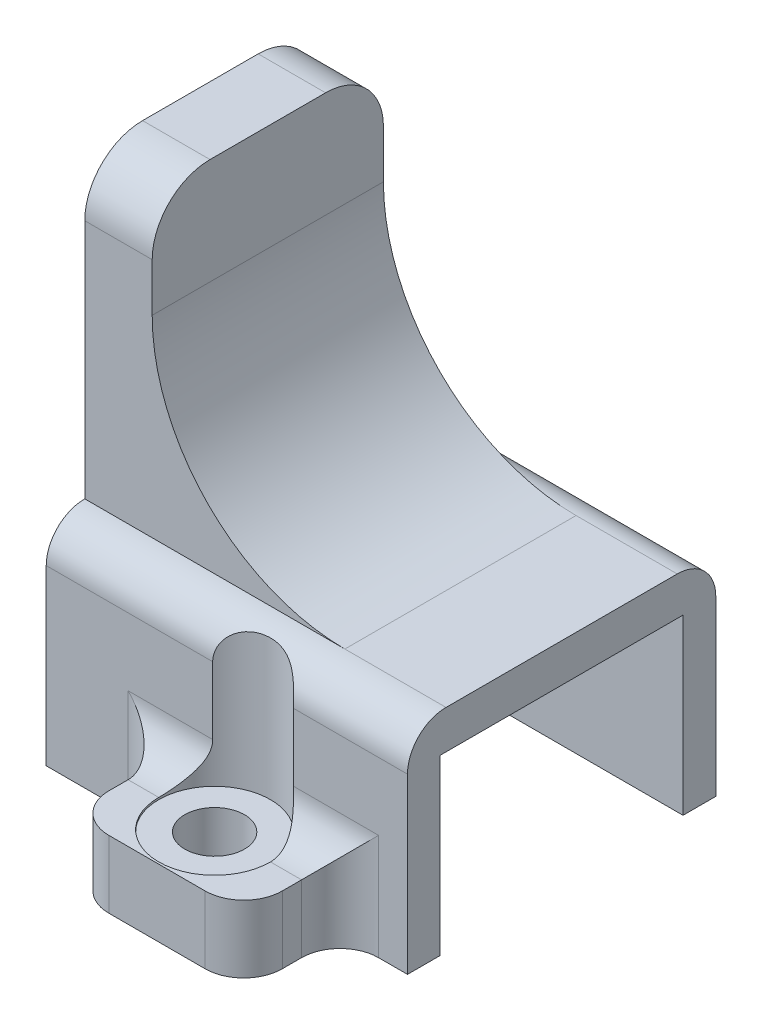
SolidWorks part; units mm, degrees
ref_plane "Alzado" through (0, 0, 0) normal (0, 0, 1) x (1, 0, 0)
ref_plane "Planta" through (0, 0, 0) normal (0, 1, 0) x (1, 0, 0)
ref_plane "Vista lateral" through (0, 0, 0) normal (1, 0, 0) x (0, 0, -1)
sketch "Croquis1" plane through (0, 0, 0) normal (0, 1, 0) x (1, 0, 0)
  line L1 (0, 0) -> (18.75, 0)
  line L2 (0, 0) -> (0, 16)
  line L3 (0, 16) -> (18.75, 16)
  line L4 (18.75, 0) -> (18.75, 16)
  dimension "D1" = 18.75
  dimension "D2" = 16
extrude "Saliente-Extruir1" add sketch "Croquis1" along normal blind 10
sketch "Croquis2" plane through (0, 0, 0) normal (0, -1, 0) x (1, 0, 0)
  line L19 (18.75, 0) -> (18.75, -16) construction
  line L20 (0, -16) -> (0, 0) construction
  line L22 (0, 0) -> (18.75, 0) construction
  line L23 (0, -1.7) -> (18.75, -1.7)
  line L24 (0, -1.7) -> (0, -14.3)
  line L25 (0, -14.3) -> (18.75, -14.3)
  line L26 (18.75, -1.7) -> (18.75, -14.3)
  line L27 (18.75, -16) -> (0, -16) construction
  point P10 (9.375, 0)
  dimension "D1" = 1.7
  dimension "D2" = 1.7
extrude "Cortar-Extruir1" cut sketch "Croquis2" against normal blind 8
sketch "Croquis3" plane through (0, 0, 0) normal (0, 0, 1) x (1, 0, 0)
  line L0 (0, 0) -> (18.75, 0) construction
  line L1 (6.25, 0) -> (15.25, 0)
  line L2 (6.25, 0) -> (6.25, 2.5)
  line L3 (6.25, 2.5) -> (15.25, 2.5)
  line L4 (15.25, 0) -> (15.25, 2.5)
  line L5 (18.75, 10) -> (18.75, 0) construction
  dimension "D1" = 2.5
  dimension "D2" = 3.5
  dimension "D3" = 9
extrude "Saliente-Extruir2" add sketch "Croquis3" along normal blind 5
sketch "Croquis4" plane through (0, 2.5, 0) normal (0, 1, 0) x (1, 0, 0)
  line L0 (18.75, 0) -> (18.75, 16) construction
  line L1 (15.25, 0) -> (6.25, 0) construction
  circle A0 centre (10.74, -2) radius 1.55
  dimension "D1" = 3.1
  dimension "D2" = 8.01
  dimension "D3" = 2
extrude "Cortar-Extruir2" cut sketch "Croquis4" against normal up to surface (2.5 mm away) up to face at (9.375, 0, -15.15)
fillet "Redondeo1" radius 2 7 edges at (9.375, 10, -16) (9.375, 10, 0) (6.25, 1.25, 5) (15.25, 1.25, 5) (10.75, 2.5, 0) (15.25, 1.25, 0) (6.25, 1.25, 0)
sketch "Croquis5" plane through (0, 10, 0) normal (0, 1, 0) x (1, 0, 0)
  circle A0 centre (10.74, -2) radius 2.9
  dimension "D1" = 5.8
extrude "Cortar-Extruir3" cut sketch "Croquis5" against normal blind 7.6
sketch "Croquis6" plane through (0, 10, 0) normal (0, 1, 0) x (1, 0, 0)
  line L0 (0, 2) -> (18.75, 2) construction
  line L1 (0, 14) -> (3.5, 14)
  line L2 (0, 14) -> (0, 2)
  line L3 (0, 2) -> (3.5, 2)
  line L4 (3.5, 14) -> (3.5, 2)
  dimension "D1" = 3.5
extrude "Saliente-Extruir3" add sketch "Croquis6" along normal blind 15.5
fillet "Redondeo2" radius 10 1 edges at (3.5, 10, -8)
fillet "Redondeo3" radius 3 2 edges at (1.75, 25.5, -14) (1.75, 25.5, -2)
sketch "Croquis7" plane through (0, 0, 0) normal (-1, 0, 0) x (0, 0, 1)
  line L0 (-14.3, 0) -> (-14.3, 8)
  line L1 (-14.3, 8) -> (-1.7, 8)
  line L2 (-1.7, 8) -> (-1.7, 0)
  line L10 (-5, 25.5) -> (-11, 25.5)
  line L11 (-14, 22.5) -> (-14, 10)
  line L12 (-16, 8) -> (-16, 0)
  line L13 (-16, 0) -> (-14.3, 0)
  line L14 (-14.3, 0) -> (-14.3, 8)
  line L15 (-14.3, 8) -> (-1.7, 8)
  line L16 (-1.7, 8) -> (-1.7, 0)
  line L17 (-1.7, 0) -> (0, 0)
  line L18 (0, 0) -> (0, 8)
  line L19 (-2, 10) -> (-2, 22.5)
  line L20 (-5, 25.5) -> (-11, 25.5)
  line L21 (-14, 22.5) -> (-14, 10)
  line L22 (-16, 8) -> (-16, 0)
  line L23 (-16, 0) -> (-14.3, 0)
  line L27 (-1.7, 0) -> (0, 0)
  line L28 (0, 0) -> (0, 8)
  line L29 (-2, 10) -> (-2, 22.5)
  arc A4 (-11, 25.5) -> (-14, 22.5) centre (-11, 22.5) ccw
  arc A5 (-14, 10) -> (-16, 8) centre (-14, 8) ccw
  arc A6 (0, 8) -> (-2, 10) centre (-2, 8) ccw
  arc A7 (-2, 22.5) -> (-5, 25.5) centre (-5, 22.5) ccw
  arc A8 (-11, 25.5) -> (-14, 22.5) centre (-11, 22.5) ccw
  arc A9 (-14, 10) -> (-16, 8) centre (-14, 8) ccw
  arc A10 (0, 8) -> (-2, 10) centre (-2, 8) ccw
  arc A11 (-2, 22.5) -> (-5, 25.5) centre (-5, 22.5) ccw
  dimension "D1" = 0
sketch "Croquis8" plane through (0, 0, 0) normal (0, -1, 0) x (1, 0, 0)
  line L4 (18.75, -14.3) -> (-5, -14.3)
  line L5 (-5, -14.3) -> (-5, -16)
  line L6 (-5, -16) -> (18.75, -16)
  line L7 (18.75, -16) -> (18.75, -14.3)
  line L8 (13.25, 5) -> (8.25, 5)
  line L9 (6.25, 3) -> (6.25, 2)
  line L10 (4.25, 0) -> (-5, 0)
  line L11 (-5, 0) -> (-5, -1.7)
  line L12 (-5, -1.7) -> (18.75, -1.7)
  line L13 (18.75, -1.7) -> (18.75, 0)
  line L14 (18.75, 0) -> (17.25, 0)
  line L15 (15.25, 2) -> (15.25, 3)
  line L16 (13.25, 5) -> (8.25, 5)
  line L17 (6.25, 3) -> (6.25, 2)
  line L18 (4.25, 0) -> (-5, 0)
  line L19 (-5, 0) -> (-5, -1.7)
  line L20 (-5, -1.7) -> (18.75, -1.7)
  line L21 (18.75, -1.7) -> (18.75, 0)
  line L22 (18.75, 0) -> (17.25, 0)
  line L23 (15.25, 2) -> (15.25, 3)
  line L24 (18.75, -14.3) -> (-5, -14.3)
  line L25 (-5, -14.3) -> (-5, -16)
  line L26 (-5, -16) -> (18.75, -16)
  line L27 (18.75, -16) -> (18.75, -14.3)
  circle A0 centre (10.74, 2) radius 1.55 construction
  circle A1 centre (10.74, 2) radius 1.55
  arc A4 (8.25, 5) -> (6.25, 3) centre (8.25, 3) ccw
  arc A5 (4.25, 0) -> (6.25, 2) centre (4.25, 2) ccw
  arc A6 (15.25, 2) -> (17.25, 0) centre (17.25, 2) ccw
  arc A7 (15.25, 3) -> (13.25, 5) centre (13.25, 3) ccw
  arc A8 (8.25, 5) -> (6.25, 3) centre (8.25, 3) ccw
  arc A9 (4.25, 0) -> (6.25, 2) centre (4.25, 2) ccw
  arc A10 (15.25, 2) -> (17.25, 0) centre (17.25, 2) ccw
  arc A11 (15.25, 3) -> (13.25, 5) centre (13.25, 3) ccw
  dimension "D1" = 0
  dimension "D2" = 0
extrude "Saliente-Extruir5" add sketch "Croquis8" along normal blind 1
sketch "Croquis9" plane through (0, 0, 0) normal (0, 1, 0) x (1, 0, 0)
  line L4 (-5, 14.3) -> (0, 14.3)
  line L5 (0, 14.3) -> (0, 16)
  line L6 (0, 16) -> (-5, 16)
  line L7 (-5, 16) -> (-5, 14.3)
  line L8 (-5, 14.3) -> (0, 14.3)
  line L9 (0, 14.3) -> (0, 16)
  line L10 (0, 16) -> (-5, 16)
  line L11 (-5, 16) -> (-5, 14.3)
  line L12 (-5, 0) -> (0, 0)
  line L13 (0, 0) -> (0, 1.7)
  line L14 (0, 1.7) -> (-5, 1.7)
  line L15 (-5, 1.7) -> (-5, 0)
  line L16 (-5, 0) -> (0, 0)
  line L17 (0, 0) -> (0, 1.7)
  line L18 (0, 1.7) -> (-5, 1.7)
  line L19 (-5, 1.7) -> (-5, 0)
  dimension "D1" = 0
  dimension "D2" = 0
extrude "Cortar-Extruir4" cut sketch "Croquis9" against normal through all
